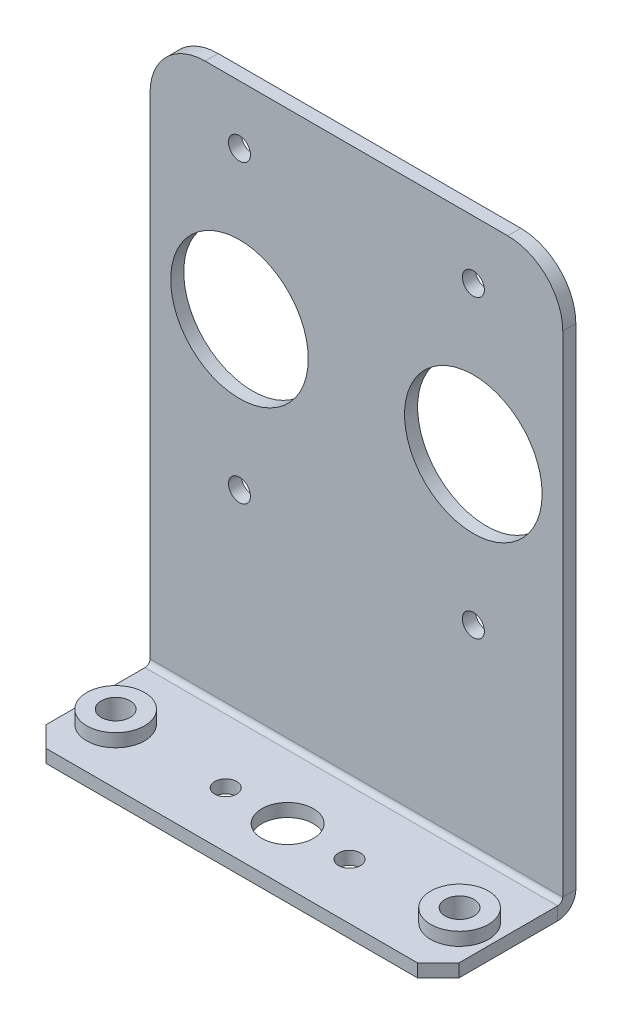
SolidWorks part; units mm, degrees
note: The reader was unsure of these and kept them because the rebuilt part matched: flange length of "边线-法兰1".
ref_plane "前视基准面" through (0, 0, 0) normal (0, 0, 1) x (1, 0, 0)
ref_plane "上视基准面" through (0, 0, 0) normal (0, 1, 0) x (1, 0, 0)
ref_plane "右视基准面" through (0, 0, 0) normal (1, 0, 0) x (0, 0, -1)
sketch "草图1" plane through (0, 0, 0) normal (0, 0, 1) x (1, 0, 0)
  line L0 (0, 96.6397) -> (0, -92.3558) construction
  line L2 (-22, 80) -> (22, 80)
  line L3 (-30, 72) -> (-30, 0)
  line L4 (-30, 0) -> (30, 0)
  line L5 (30, 72) -> (30, 0)
  arc A0 (-30, 72) -> (-22, 80) centre (-22, 72) cw
  arc A1 (30, 72) -> (22, 80) centre (22, 72) ccw
  point P9 (-30, 80)
  point P12 (30, 80)
  dimension "D3" = 8
  dimension "D4" = 8
  dimension "D1" = 60
  dimension "D2" = 80
sheet metal parameters "钣金1" thickness 1.9 parameters "D1"=0.7366
base flange "基体-法兰1" sketch "草图1" thickness 1.9 reverse thickness direction no parameters "D1"=0.7366
edge flange "边线-法兰1" sketch "草图7" flange angle 90 flange length 20 flange position material outside bend radius 0.7366 thickness 1.9 relief rectangular parameters "D6"=10
sketch "草图7" plane through (0, 0, 0) normal (0, -1, 0) x (1, 0, 0)
  line L2 (-30, 0) -> (-30, 18.1)
  line L3 (-30, 18.1) -> (30, 18.1)
  line L4 (30, 18.1) -> (30, 0)
  line L5 (-30, 0) -> (30, 0) construction
  line L6 (-30, 0) -> (30, 0)
bend "边线折弯1" bend radius 0.7366 bend angle 90 parameters "D5"=1
sketch "草图8" plane through (0, 0, 0) normal (0, 1, 0) x (1, 0, 0)
  line L0 (-30, -15.1) -> (-27, -18.1)
  line L1 (-30, 0) -> (-30, -18.1) construction
  line L2 (30, -18.1) -> (-30, -18.1) construction
  line L3 (27, -18.1) -> (30, -15.1)
  line L4 (30, -0.7366) -> (30, -18.1) construction
  line L5 (-30, -15.1) -> (-30, -18.1)
  line L6 (-30, -18.1) -> (-27, -18.1)
  line L7 (27, -18.1) -> (30, -18.1)
  line L8 (30, -18.1) -> (30, -15.1)
  dimension "D1" = 3
  dimension "D2" = 3
  dimension "D3" = 3
  dimension "D4" = 3
extrude "切除-拉伸1" cut sketch "草图8" against normal through all normal cut yes
sketch "草图9" plane through (0, 0, 0) normal (0, 1, 0) x (1, 0, 0)
  line L0 (-37.1888, -10) -> (42.961, -10) construction
  line L1 (0, 8.1043) -> (0, -23.1619) construction
  line L2 (-30, -15.1) -> (-30, -0.7366) construction
  circle A0 centre (-25, -10) radius 2.1
  circle A1 centre (-9, -10) radius 1.6
  circle A2 centre (0, -10) radius 3.75
  circle A3 centre (9, -10) radius 1.6
  circle A4 centre (25, -10) radius 2.1
  dimension "D3" = 4.2
  dimension "D5" = 3.2
  dimension "D6" = 7.5
  dimension "D1" = 10
  dimension "D2" = 5
  dimension "D4" = 21
extrude "切除-拉伸2" cut sketch "草图9" against normal through all normal cut yes
sketch "草图10" plane through (0, 0, 0) normal (0, 1, 0) x (1, 0, 0)
  line L6 (-30, -0.7366) -> (-30, -15.1)
  line L7 (-30, -15.1) -> (-27, -18.1)
  line L8 (-27, -18.1) -> (27, -18.1)
  line L9 (27, -18.1) -> (30, -15.1)
  line L10 (30, -15.1) -> (30, -0.7366)
  line L11 (30, -0.7366) -> (-30, -0.7366)
  line L12 (-30, -0.7366) -> (-30, -15.1)
  line L13 (-30, -15.1) -> (-27, -18.1)
  line L14 (-27, -18.1) -> (27, -18.1)
  line L15 (27, -18.1) -> (30, -15.1)
  line L16 (30, -15.1) -> (30, -0.7366)
  line L17 (30, -0.7366) -> (-30, -0.7366)
  circle A0 centre (-25, -10) radius 2.1 construction
  circle A1 centre (25, -10) radius 2.1 construction
  circle A2 centre (-25, -10) radius 2.1
  circle A3 centre (25, -10) radius 2.1
  circle A4 centre (-25, -10) radius 4.2
  circle A5 centre (25, -10) radius 4.2
  circle M7 centre (25, -10) radius 2.1
  circle M11 centre (-25, -10) radius 2.1
  dimension "D2" = 8.4
  dimension "D3" = 8.4
  dimension "D1" = 0
extrude "凸台-拉伸2" add sketch "草图10" along normal blind 1.9 contours A4 M11 | A5 M7
sketch "草图11" plane through (0, 0, 0) normal (0, 0, 1) x (1, 0, 0)
  line L0 (22, 80) -> (-22, 80) construction
  line L1 (-46.5145, 50) -> (49.8018, 50) construction
  line L2 (0, 82.0316) -> (0, -6.5118) construction
  line L3 (-30, 72) -> (-30, 0.7366) construction
  circle A0 centre (-17, 71.5) radius 1.6
  circle A1 centre (-17, 50) radius 10
  circle A2 centre (-17, 28.5) radius 1.6
  circle A3 centre (17, 28.5) radius 1.6
  circle A4 centre (17, 50) radius 10
  circle A5 centre (17, 71.5) radius 1.6
  dimension "D3" = 3.2
  dimension "D6" = 20
  dimension "D1" = 30
  dimension "D2" = 8.5
  dimension "D4" = 13
  dimension "D5" = 13
extrude "切除-拉伸3" cut sketch "草图11" against normal through all normal cut yes
flat pattern "平板型式1" [suppressed]
sketch "折弯-线1" plane through (0, 0, 0) normal (0, 1, 0) x (-1, 0, 0)
sketch3d "边界框1" [suppressed]
  line L0 (8, 8, 0) -> (8, -72, 0) construction
  line L1 (-52, 8, 0) -> (-52, -72, 0) construction
  line L2 (8, 8, 0) -> (-52, 8, 0) construction
  line L3 (8, -72, 0) -> (-52, -72, 0) construction
bend of the flat pattern "展开-<边线折弯1>1"
